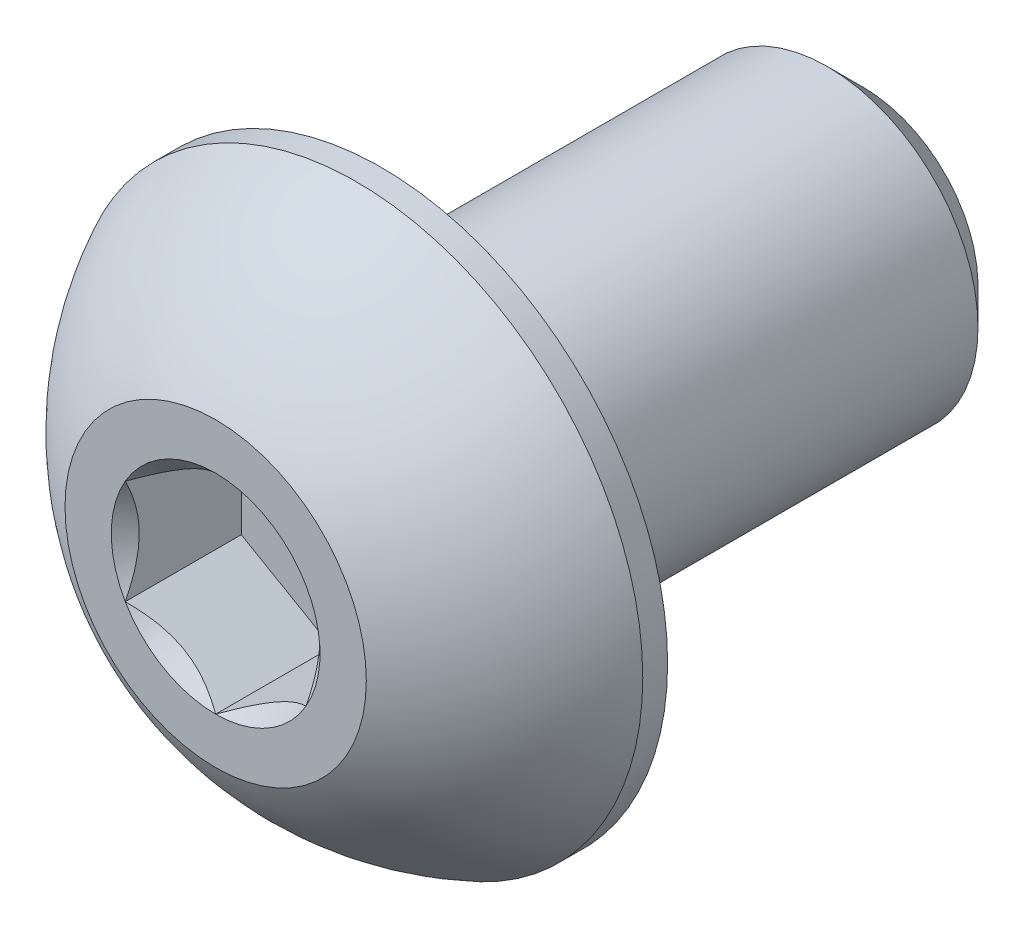
SolidWorks part; units mm, degrees
ref_plane "Front" through (0, 0, 0) normal (0, 0, 1) x (1, 0, 0)
ref_plane "Top" through (0, 0, 0) normal (0, 1, 0) x (1, 0, 0)
ref_plane "Right" through (0, 0, 0) normal (1, 0, 0) x (0, 0, -1)
sketch "Sketch1" plane through (0, 0, 0) normal (1, 0, 0) x (0, 0, -1)
  line L2 (2.75, 2.5) -> (10.75, 2.5)
  line L3 (10.75, 2.5) -> (10.75, 0)
  line L4 (10.75, 0) -> (2.75, 0)
  line L6 (2.3375, 4.75) -> (2.75, 4.75) construction
  line L7 (10.75, 2.5) -> (10.75, -2.5) construction
  line L8 (0, 0) -> (2.75, 0) construction
  line L9 (2.75, 4.75) -> (2.75, -4.75) construction
  line L11 (2.75, 2.5) -> (2.75, 0)
  line L13 (0, 1.5) -> (0, -1.5) construction
  line L14 (0, 1.5) -> (0, 2.5) construction
  arc A3 (0, 2.5) -> (2.3375, 4.75) centre (4.6581, 0) cw construction
  dimension "D1" = 0.4125
revolve "Revolve1" add sketch "Sketch1" angle 360 mid plane about L4
sketch "Sketch3" plane through (0, 0, -10.75) normal (0, 0, -1) x (-1, 0, 0)
  circle A0 centre (0, 0) radius 2.5
curve "Helix/Spiral1" pitch 0.8 height 8.8 turns 11
sketch "Sketch2" plane through (0, 0, 0) normal (1, 0, 0) x (0, 0, -1)
  line L0 (10.75, 2.5) -> (11.45, 2.5)
  line L1 (11.45, 2.5) -> (11.15, 1.9804)
  line L2 (11.15, 1.9804) -> (11.05, 1.9804)
  line L3 (11.05, 1.9804) -> (10.75, 2.5)
  line L4 (10.9, 2.2402) -> (11.3, 2.2402) construction
  dimension "D1" = 60
  dimension "D2" = 0.1
  dimension "D3" = 0.4
chamfer "Chamfer1" distance 0.6 angle 45 1 edges at (0, 2.5, -10.75)
sweep "Cut-Sweep1" [suppressed] cut profiles "Sketch2" path "Helix/Spiral1"
sketch "Sketch7" plane through (0, 0, 0) normal (1, 0, 0) x (0, 0, -1)
  line L6 (2.3375, 4.75) -> (2.75, 4.75) construction
  line L8 (0, 0) -> (2.75, 0) construction
  line L11 (2.75, 4.75) -> (2.75, -4.75) construction
  line L12 (2.3375, 4.75) -> (2.75, 4.75)
  line L13 (0, 0) -> (2.75, 0)
  line L14 (0, 1.5) -> (0, -1.5) construction
  line L15 (2.75, 4.75) -> (2.75, 0)
  line L16 (0, 2.5) -> (0, 0)
  arc A2 (2.3375, 4.75) -> (0, 2.5) centre (4.6581, 0) ccw construction
  arc A3 (2.3375, 4.75) -> (0, 2.5) centre (4.6581, 0) ccw
revolve "Revolve2" add sketch "Sketch7" angle 360 mid plane about L13
sketch "Sketch5" plane through (0, 0, 0) normal (0, 0, 1) x (1, 0, 0)
  line L1 (1.5, -0.866) -> (1.5, 0.866)
  line L2 (1.5, 0.866) -> (0, 1.7321)
  line L3 (0, 1.7321) -> (-1.5, 0.866)
  line L4 (-1.5, 0.866) -> (-1.5, -0.866)
  line L5 (-1.5, -0.866) -> (0, -1.7321)
  line L6 (0, -1.7321) -> (1.5, -0.866)
  circle A0 centre (0, 0) radius 1.5 construction
extrude "Cut-Extrude2" cut sketch "Sketch5" against normal blind 1.925
sketch "Sketch6" plane through (0, 0, 0) normal (0, 0, 1) x (1, 0, 0)
  circle A0 centre (0, 0) radius 1.7321
extrude "Cut-Extrude3" cut sketch "Sketch6" against normal blind 1.925 draft 45
sketch "Sketch9" [suppressed] plane through (0, 0, -2.75) normal (0, 0, 1) x (1, 0, 0)
  circle A2 centre (0, 0) radius 2.5
extrude "Boss-Extrude2" [suppressed] add sketch "Sketch9" against normal offset from surface (13 mm away) 20
sketch "Sketch10" plane through (0, 0, 0) normal (1, 0, 0) x (0, 0, -1)
  line L0 (10.75, 2.5) -> (10.75, -2.5) construction
  point P0 (9.55, -2.5)
  dimension "D1" = 1.2
equation "\"D3@Helix/Spiral1\" = \"Lg@Sketch1\" + \"D4@Helix/Spiral1\""
equation "\"D2@Sketch2\" = \"D4@Helix/Spiral1\" * .125"
equation "\"D3@Sketch2\" = \"D4@Helix/Spiral1\" * .5"
equation "\"D1@Chamfer1\" = \"D4@Helix/Spiral1\" * .75"
equation "\"D1@Cut-Extrude2\" = \"Head Ht@Sketch1\" * .7"
equation "\"D1@Sketch1\" = \"Head Ht@Sketch1\" * .15"
equation "\"D1@Sketch10\" = \"D4@Helix/Spiral1\" * 1.5"
equation "\"D1@Cut-Extrude3\" = \"D1@Cut-Extrude2\""
